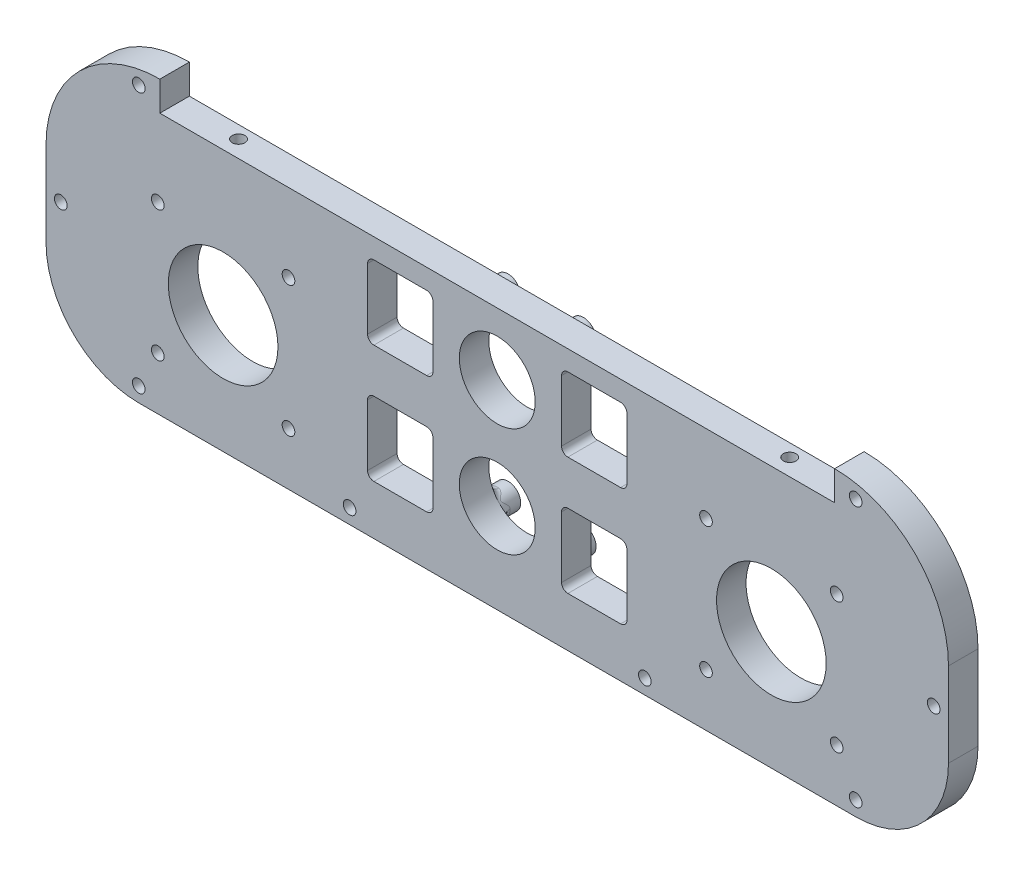
SolidWorks part; units mm, degrees
ref_plane "Piano frontale" through (0, 0, 0) normal (0, 0, 1) x (1, 0, 0)
ref_plane "Piano superiore" through (0, 0, 0) normal (0, 1, 0) x (1, 0, 0)
ref_plane "Piano destro" through (0, 0, 0) normal (1, 0, 0) x (0, 0, -1)
sketch "Schizzo1" plane through (0, 0, 0) normal (0, 0, 1) x (1, 0, 0)
  line L0 (-65, -6.5002) -> (-49.5002, 8.9996) construction
  line L1 (49.5002, -22) -> (50.8579, -20.6424) construction
  line L2 (50.8579, 7.6419) -> (49.5002, 8.9996) construction
  line L3 (-65, -6.5002) -> (-80.4998, -22) construction
  line L4 (-65, -6.5002) -> (-49.5002, -22) construction
  line L5 (-65, -6.5002) -> (-80.4998, 8.9996) construction
  line L6 (-65, -6.5002) -> (-65, 22.4998) construction
  line L7 (65, -6.5002) -> (80.4998, 8.9996) construction
  line L8 (65, -6.5002) -> (80.4998, -22) construction
  line L9 (65, -6.5002) -> (65, 22.4998) construction
  line L10 (-65, -6.5002) -> (65, -6.5002) construction
  line L11 (80, 34.5) -> (-80, 34.5)
  line L12 (80, 27.5) -> (-80, 27.5)
  line L13 (100, 7.5) -> (100, -12.5)
  line L14 (85, -27.5) -> (-85, -27.5)
  line L15 (-100, 7.5) -> (-100, -12.5)
  line L16 (100, 27.5) -> (-100, -27.5) construction
  line L17 (100, -27.5) -> (-100, 27.5) construction
  line L18 (-107, 7.5) -> (-107, -12.5)
  line L19 (85, -34.5) -> (-85, -34.5)
  line L20 (107, 7.5) -> (107, -12.5)
  circle A0 centre (-65, -6.5002) radius 13
  circle A1 centre (65, -6.5002) radius 13
  circle A2 centre (-49.5002, 8.9996) radius 1.5
  circle A3 centre (-49.5002, -22) radius 1.5
  circle A4 centre (-80.4998, -22) radius 1.5
  circle A5 centre (-80.4998, 8.9996) radius 1.5
  circle A6 centre (49.5002, -22) radius 1.5
  circle A7 centre (80.4998, -22) radius 1.5
  circle A8 centre (80.4998, 8.9996) radius 1.5
  circle A9 centre (49.5002, 8.9996) radius 1.5
  arc A10 (-80, 27.5) -> (-100, 7.5) centre (-80, 7.5) ccw
  arc A11 (50.8579, -20.6424) -> (50.8579, 7.6419) centre (36.7157, -6.5002) ccw construction
  arc A12 (100, 7.5) -> (80, 27.5) centre (80, 7.5) ccw
  arc A13 (-85, -27.5) -> (-100, -12.5) centre (-85, -12.5) cw
  arc A14 (100, -12.5) -> (85, -27.5) centre (85, -12.5) cw
  arc A15 (-80, 34.5) -> (-107, 7.5) centre (-80, 7.5) ccw
  arc A16 (-85, -34.5) -> (-107, -12.5) centre (-85, -12.5) cw
  arc A17 (107, -12.5) -> (85, -34.5) centre (85, -12.5) cw
  arc A18 (107, 7.5) -> (80, 34.5) centre (80, 7.5) ccw
  point P0 (0, -6.5002)
  point P1 (0, -6.5002)
  point P2 (0, 0)
  dimension "D1" = 3
  dimension "D2" = 3
  dimension "D3" = 3
  dimension "D4" = 3
  dimension "D5" = 3
  dimension "D6" = 3
  dimension "D8" = 26
  dimension "D9" = 26
  dimension "D12" = 3
  dimension "D13" = 3
  dimension "D24" = 20
  dimension "D25" = 20
  dimension "D26" = 15
  dimension "D27" = 15
  dimension "D7" = 45
  dimension "D10" = 21.92
  dimension "D11" = 21.92
  dimension "D14" = 21.92
  dimension "D15" = 21.92
  dimension "D16" = 21.92
  dimension "D17" = 45
  dimension "D18" = 21.92
  dimension "D19" = 21.92
  dimension "D20" = 21.92
  dimension "D21" = 90
  dimension "D22" = 55
  dimension "D23" = 5.5
  dimension "D28" = 65
  dimension "D29" = 65
extrude "Estrusione-Estrusione1" add sketch "Schizzo1" along normal blind 7 contours L11 A15 L18 A16 L19 A17 L20 A18 | A0 | A5 | A2 | A4 | A3 | A9 | A1 | A8 | A7 | A6
sketch "Schizzo2" plane through (0, 0, 7) normal (0, 0, 1) x (1, 0, 0)
  line L0 (0, 0) -> (0, 34.5) construction
  line L1 (80, 34.5) -> (-80, 34.5) construction
  line L2 (0, 34.5) -> (0, 27.5) construction
  line L3 (0, 27.5) -> (80, 27.5)
  line L4 (80, 27.5) -> (80, 34.5)
  line L5 (0, 27.5) -> (-80, 27.5)
  line L6 (-80, 27.5) -> (-80, 34.5)
  line L7 (-80, 34.5) -> (80, 34.5)
  dimension "D1" = 7
  dimension "D2" = 80
  dimension "D3" = 80
extrude "Taglio-Estrusione1" cut sketch "Schizzo2" against normal blind 7
sketch "Schizzo4" plane through (0, 0, 0) normal (0, 0, -1) x (-1, 0, 0)
  line L1 (0, -0.2335) -> (0, 34.5) construction
  line L3 (-80, 34.5) -> (80, 34.5) construction
  circle A0 centre (0, -13.1748) radius 9
  circle A1 centre (0, 12.7078) radius 9
  point P13 (0, 34.5)
  dimension "D1" = 18
  dimension "D8" = 18
  dimension "D2" = 12.9413
  dimension "D3" = 34.7335
  dimension "D4" = 0
  dimension "D5" = 0
  dimension "D6" = 12.9413
  dimension "D7" = 25.8826
extrude "Taglio-Estrusione2" cut sketch "Schizzo4" against normal blind 7
sketch "Schizzo5" plane through (0, 0, 0) normal (0, 0, -1) x (-1, 0, 0)
  line L0 (-8.9408, 21.2852) -> (-8.9408, -21.2852) construction
  line L1 (8.9408, 21.2852) -> (-8.9408, 21.2852) construction
  line L2 (8.9408, 21.2852) -> (8.9408, -21.2852) construction
  line L3 (-8.9408, 21.2852) -> (8.9408, -21.2852) construction
  line L5 (8.9408, -21.2852) -> (-8.9408, -21.2852) construction
  circle A0 centre (-8.9408, 21.2852) radius 0.825
  circle A1 centre (-8.9408, 21.2852) radius 3
  circle A2 centre (8.9408, 21.2852) radius 0.825
  circle A3 centre (8.9408, 21.2852) radius 3
  circle A4 centre (8.9408, -21.2852) radius 3
  circle A5 centre (8.9408, -21.2852) radius 0.825
  circle A6 centre (-8.9408, -21.2852) radius 0.825
  circle A7 centre (-8.9408, -21.2852) radius 3
  point P2 (0, 0)
  dimension "D3" = 1.65
  dimension "D4" = 6
  dimension "D2" = 6
  dimension "D5" = 1.65
  dimension "D6" = 6
  dimension "D8" = 1.65
  dimension "D9" = 6
  dimension "D10" = 1.65
  dimension "D1" = 42.5704
  dimension "D7" = 17.8816
  dimension "D11" = 0
  dimension "D12" = 0
extrude "Estrusione-Estrusione2" add sketch "Schizzo5" along normal blind 4.5
fillet "Raccordo1" radius 2 4 edges at (-5.9408, -21.2852, 0) (11.9408, -21.2852, 0) (-5.9408, 21.2852, 0) (11.9408, 21.2852, 0)
sketch "Schizzo6" plane through (0, 27.5, 0) normal (0, 1, 0) x (1, 0, 0)
  line L0 (65.3439, -7) -> (65.3439, -3) construction
  line L1 (-80, -7) -> (80, -7) construction
  line L2 (65.3439, -3) -> (80, -3) construction
  line L3 (80, -7) -> (80, 0) construction
  line L4 (0, -7) -> (0, 0) construction
  circle A0 centre (65.3439, -3) radius 1.5
  circle A1 centre (-65.3439, -3) radius 1.5
  dimension "D3" = 3
  dimension "D1" = 4
  dimension "D2" = 14.6561
extrude "Taglio-Estrusione3" cut sketch "Schizzo6" against normal blind 5
sketch "Schizzo7" plane through (0, 0, 7) normal (0, 0, 1) x (1, 0, 0)
  line L0 (-85, -34.5) -> (-85, -27.5) construction
  line L1 (85, -34.5) -> (85, -27.5) construction
  line L2 (85, -27.5) -> (-85, -27.5) construction
  line L3 (-107, -12.5) -> (-100, -12.5) construction
  line L4 (-100, -12.5) -> (-100, 7.5) construction
  line L5 (-100, 7.5) -> (-107, 7.5) construction
  line L6 (0, 27.5) -> (0, -34.5) construction
  line L7 (-80, 27.5) -> (80, 27.5) construction
  line L8 (-80, 27.5) -> (-98.1384, 27.5) construction
  line L9 (-107, 7.5) -> (-100, -12.5) construction
  line L10 (-35, -27.5) -> (-35, -34.5) construction
  line L11 (85, -34.5) -> (-85, -34.5) construction
  line L12 (-85, 27.5) -> (-85, 34.033) construction
  arc A0 (-107, -12.5) -> (-85, -34.5) centre (-85, -12.5) ccw construction
  circle A2 centre (-103.5, -2.5) radius 1.5
  circle A3 centre (-85, -31) radius 1.5
  circle A4 centre (-35, -31) radius 1.5
  arc A5 (-80, 34.5) -> (-107, 7.5) centre (-80, 7.5) ccw construction
  circle A6 centre (-85, 30.7665) radius 1.5
  circle A7 centre (35, -31) radius 1.5
  circle A8 centre (85, -31) radius 1.5
  circle A9 centre (103.5, -2.5) radius 1.5
  circle A10 centre (85, 30.7665) radius 1.5
  dimension "D5" = 3
  dimension "D6" = 3
  dimension "D7" = 3
  dimension "D8" = 3
  dimension "D1" = 7
  dimension "D2" = 7
  dimension "D3" = 7
  dimension "D4" = 50
extrude "Taglio-Estrusione4" cut sketch "Schizzo7" against normal blind 33
sketch "Schizzo8" plane through (0, 0, 7) normal (0, 0, 1) x (1, 0, 0)
  line L0 (-30.75, -6.75) -> (-15.25, -21.25) construction
  line L1 (-15.25, -6.75) -> (-15.25, -21.25)
  line L2 (-16.75, -5.25) -> (-29.25, -5.25)
  line L3 (-30.75, -6.75) -> (-30.75, -21.25)
  line L4 (-29.25, -22.75) -> (-16.75, -22.75)
  line L5 (-30.75, -21.25) -> (-15.25, -6.75) construction
  line L6 (0, 0) -> (-23, 0) construction
  line L7 (-23, 0) -> (-23, -34.5) construction
  line L8 (85, -34.5) -> (-85, -34.5) construction
  line L9 (-30.75, 21.25) -> (-15.25, 6.75) construction
  line L10 (-30.75, 6.75) -> (-15.25, 21.25) construction
  line L11 (-29.25, 22.75) -> (-16.75, 22.75)
  line L12 (-30.75, 6.75) -> (-30.75, 21.25)
  line L13 (-16.75, 5.25) -> (-29.25, 5.25)
  line L14 (-15.25, 6.75) -> (-15.25, 21.25)
  line L15 (0, 0) -> (0, 27.5) construction
  line L16 (-80, 27.5) -> (80, 27.5) construction
  line L17 (30.75, 6.75) -> (15.25, 21.25) construction
  line L18 (30.75, 21.25) -> (15.25, 6.75) construction
  line L19 (30.75, -21.25) -> (15.25, -6.75) construction
  line L20 (30.75, -6.75) -> (15.25, -21.25) construction
  line L21 (15.25, 6.75) -> (15.25, 21.25)
  line L22 (16.75, 5.25) -> (29.25, 5.25)
  line L23 (30.75, 6.75) -> (30.75, 21.25)
  line L24 (29.25, 22.75) -> (16.75, 22.75)
  line L25 (29.25, -22.75) -> (16.75, -22.75)
  line L26 (30.75, -6.75) -> (30.75, -21.25)
  line L27 (16.75, -5.25) -> (29.25, -5.25)
  line L28 (15.25, -6.75) -> (15.25, -21.25)
  arc A0 (-30.75, -6.75) -> (-29.25, -5.25) centre (-29.25, -6.75) cw
  arc A1 (-16.75, -5.25) -> (-15.25, -6.75) centre (-16.75, -6.75) cw
  arc A2 (-15.25, -21.25) -> (-16.75, -22.75) centre (-16.75, -21.25) cw
  arc A3 (-29.25, -22.75) -> (-30.75, -21.25) centre (-29.25, -21.25) cw
  arc A4 (-29.25, 22.75) -> (-30.75, 21.25) centre (-29.25, 21.25) ccw
  arc A5 (-15.25, 21.25) -> (-16.75, 22.75) centre (-16.75, 21.25) ccw
  arc A6 (-16.75, 5.25) -> (-15.25, 6.75) centre (-16.75, 6.75) ccw
  arc A7 (-30.75, 6.75) -> (-29.25, 5.25) centre (-29.25, 6.75) ccw
  arc A8 (30.75, 6.75) -> (29.25, 5.25) centre (29.25, 6.75) cw
  arc A9 (16.75, 5.25) -> (15.25, 6.75) centre (16.75, 6.75) cw
  arc A10 (15.25, 21.25) -> (16.75, 22.75) centre (16.75, 21.25) cw
  arc A11 (29.25, 22.75) -> (30.75, 21.25) centre (29.25, 21.25) cw
  arc A12 (29.25, -22.75) -> (30.75, -21.25) centre (29.25, -21.25) ccw
  arc A13 (15.25, -21.25) -> (16.75, -22.75) centre (16.75, -21.25) ccw
  arc A14 (16.75, -5.25) -> (15.25, -6.75) centre (16.75, -6.75) ccw
  arc A15 (30.75, -6.75) -> (29.25, -5.25) centre (29.25, -6.75) ccw
  point P14 (-23, -14)
  dimension "D3" = 1.5
  dimension "D1" = 14.5
  dimension "D2" = 12.5
  dimension "D4" = 23
  dimension "D5" = 0
  dimension "D6" = 14
  dimension "D7" = 21.225
extrude "Taglio-Estrusione5" cut sketch "Schizzo8" against normal blind 25
